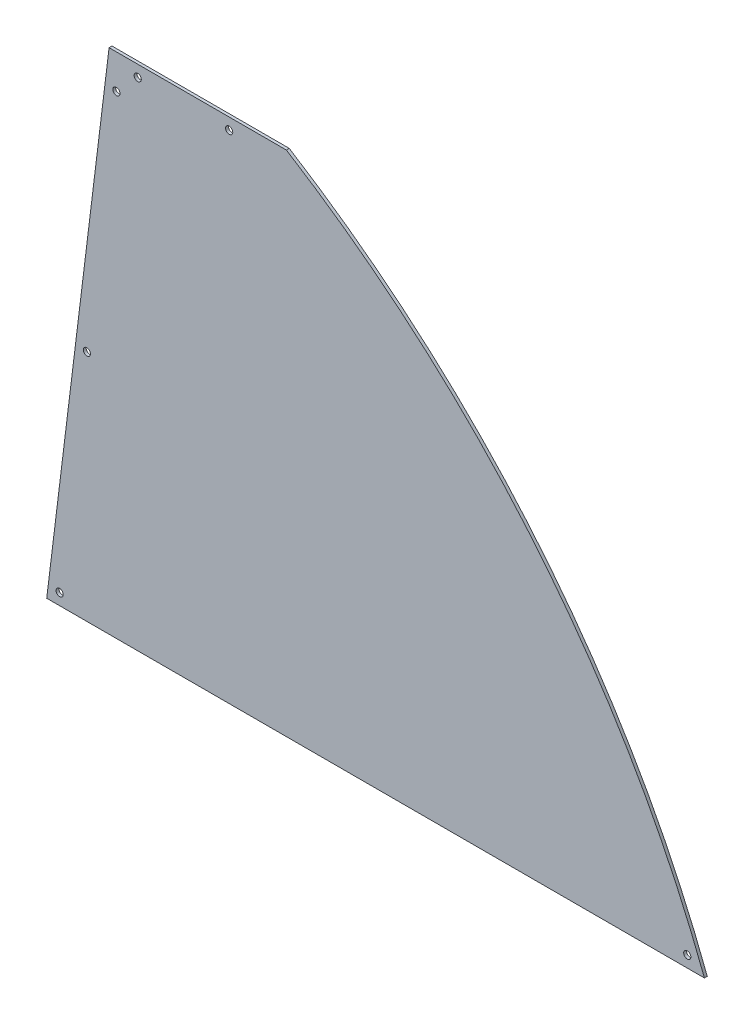
SolidWorks part; units mm, degrees
material "Pine"
ref_plane "Front Plane" through (0, 0, 0) normal (0, 0, 1) x (1, 0, 0)
ref_plane "Top Plane" through (0, 0, 0) normal (0, 1, 0) x (1, 0, 0)
ref_plane "Right Plane" through (0, 0, 0) normal (1, 0, 0) x (0, 0, -1)
sketch "Sketch2" plane through (0, 0, 0) normal (0, 0, 1) x (1, 0, 0)
  line L0 (-205.6936, 145.6238) -> (-8.8436, 145.6238) construction
  line L1 (-205.6936, 145.6238) -> (-8.8436, 145.6238)
  line L2 (-205.6936, 145.6238) -> (-274.955, -418.465)
  line L3 (-274.955, -418.465) -> (455.295, -418.465)
  arc A0 (-8.8436, 145.6238) -> (455.295, -418.465) centre (-613.1246, -824.579) cw
  dimension "D5" = 1143
  dimension "D1" = 568.325
  dimension "D2" = 730.25
  dimension "D3" = 196.85
  dimension "D4" = 83
extrude "Boss-Extrude1" add sketch "Sketch2" along normal blind 3.175
hole_wizard "5/16 (0.3125) Diameter Hole1" positions "Sketch3" profile "Sketch4" hole size "5/16" standard "ANSI Inch" end condition through all
sketch "Sketch3" plane through (0, 0, 0) normal (0, 0, -1) x (-1, 0, 0)
  line L0 (274.955, -418.465) -> (-455.295, -418.465) construction
  line L1 (205.6936, 145.6238) -> (274.955, -418.465) construction
  line L2 (8.8436, 145.6238) -> (205.6936, 145.6238) construction
  point P0 (-436.245, -405.765)
  point P2 (260.6003, -405.765)
  point P4 (230.323, -159.1762)
  point P6 (197.5763, 107.5238)
  point P20 (173.9436, 132.9238)
  point P22 (72.3436, 132.9238)
  dimension "D1" = 12.7
  dimension "D2" = 12.7
  dimension "D3" = 12.7
  dimension "D4" = 12.7
  dimension "D5" = 12.7
  dimension "D6" = 38.1
  dimension "D7" = 304.8
  dimension "D8" = 711.2
  dimension "D9" = 12.7
  dimension "D10" = 31.75
  dimension "D11" = 101.6
sketch "Sketch4" plane through (436.245, -405.765, 0) normal (1, 0, 0) x (0, 1, 0)
  line L0 (0, 0) -> (0, 3.175)
  line L1 (0, 3.175) -> (3.9687, 3.175)
  line L2 (3.9687, 3.175) -> (3.9687, 0)
  line L5 (3.9687, 0) -> (0, 0)
  line L11 (0, -6.35) -> (0, 107.95) construction
  dimension "Thru Hole Dia." = 7.9375
  dimension "Thru Hole Depth" = 3.175
